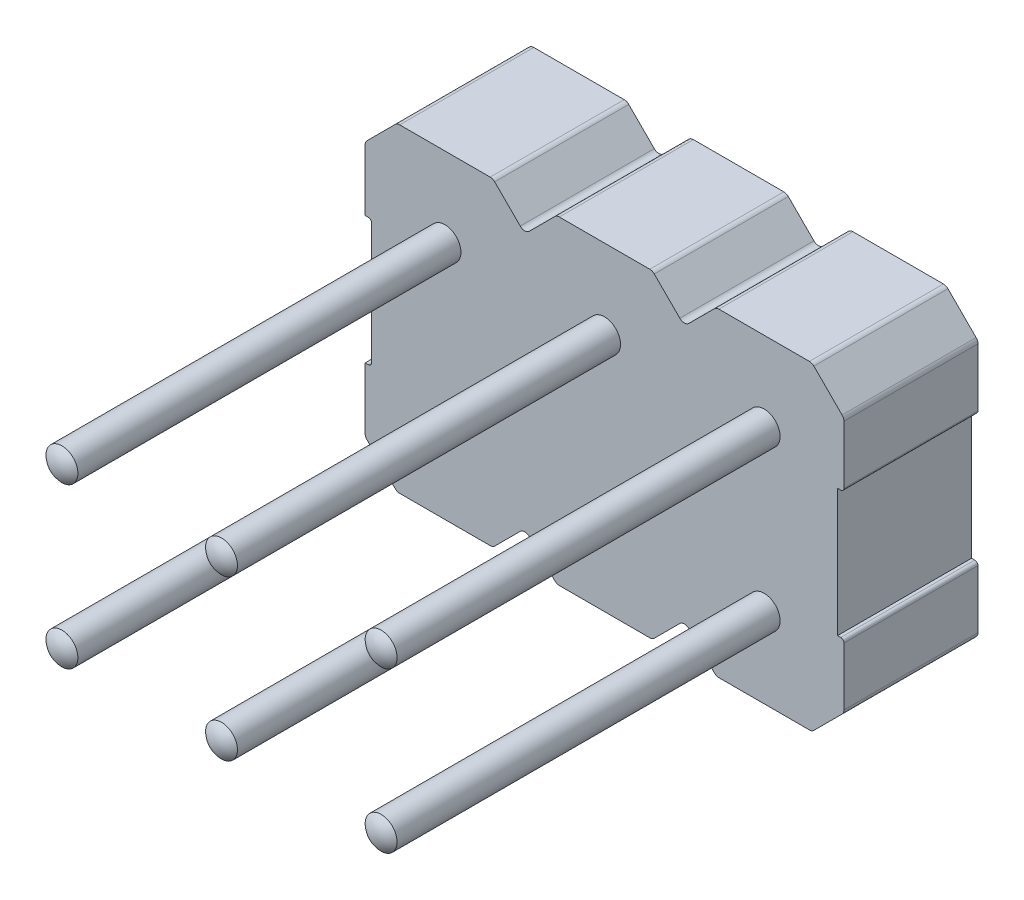
SolidWorks part; units mm, degrees
ref_plane "Plan de face" through (0, 0, 0) normal (0, 0, 1) x (1, 0, 0)
ref_plane "Plan de dessus" through (0, 0, 0) normal (0, 1, 0) x (1, 0, 0)
ref_plane "Plan de droite" through (0, 0, 0) normal (1, 0, 0) x (0, 0, -1)
sketch "Esquisse1" plane through (0, 0, 0) normal (0, 0, 1) x (1, 0, 0)
  line L0 (-1.25, 2) -> (-1.25, -2.5) construction
  line L1 (-3.2086, -2.5) -> (-1.7914, -2.5)
  line L2 (-3.75, -1.9586) -> (-3.75, -1)
  line L3 (-3.2086, 2.5) -> (-1.7914, 2.5)
  line L4 (3.75, -1.9586) -> (3.75, -1.05)
  line L5 (-3.75, -2.5) -> (3.75, 2.5) construction
  line L6 (-3.75, 2.5) -> (3.75, -2.5) construction
  line L7 (1.1793, 2.0707) -> (0.7793, 2.4707)
  line L8 (-1.7207, 2.4707) -> (-1.3207, 2.0707)
  line L9 (-1.1793, 2.0707) -> (-0.7793, 2.4707)
  line L10 (0, 0) -> (0, 1.0178) construction
  line L11 (-1.5641, 0) -> (0, 0) construction
  line L12 (1.7207, 2.4707) -> (1.3207, 2.0707)
  line L13 (1.7207, -2.4707) -> (1.3207, -2.0707)
  line L14 (1.1793, -2.0707) -> (0.7793, -2.4707)
  line L15 (-1.1793, -2.0707) -> (-0.7793, -2.4707)
  line L16 (-1.7207, -2.4707) -> (-1.3207, -2.0707)
  line L17 (-0.7086, 2.5) -> (0.7086, 2.5)
  line L18 (1.7914, 2.5) -> (3.2086, 2.5)
  line L19 (1.7914, -2.5) -> (3.2086, -2.5)
  line L20 (-0.7086, -2.5) -> (0.7086, -2.5)
  line L21 (3.7207, -2.0293) -> (3.2793, -2.4707)
  line L22 (3.7207, 2.0293) -> (3.2793, 2.4707)
  line L23 (-3.7207, -2.0293) -> (-3.2793, -2.4707)
  line L24 (-3.7207, 2.0293) -> (-3.2793, 2.4707)
  line L25 (-3.75, 1) -> (-3.75, 1.9586)
  line L26 (-3.75, -1) -> (-3.7, -1)
  line L27 (3.7, -1) -> (3.65, -1)
  line L28 (-3.75, 1) -> (-3.7, 1)
  line L29 (-3.65, -0.95) -> (-3.65, 0.95)
  line L30 (-3.75, 0) -> (-3.65, 1) construction
  line L31 (-3.75, 0) -> (-3.65, -1) construction
  line L32 (3.7, 1) -> (3.65, 1)
  line L33 (3.65, -1) -> (3.65, 1)
  line L34 (3.75, 1.05) -> (3.75, 1.9586)
  circle A0 centre (-2.5, 1.25) radius 0.25
  circle A1 centre (0, 1.25) radius 0.25
  circle A2 centre (2.5, 1.25) radius 0.25
  circle A3 centre (0, -1.25) radius 0.25
  circle A4 centre (2.5, -1.25) radius 0.25
  circle A5 centre (-2.5, -1.25) radius 0.25
  arc A6 (-3.2793, 2.4707) -> (-3.2086, 2.5) centre (-3.2086, 2.4) cw
  arc A7 (-3.7207, 2.0293) -> (-3.75, 1.9586) centre (-3.65, 1.9586) ccw
  arc A8 (-3.7207, -2.0293) -> (-3.75, -1.9586) centre (-3.65, -1.9586) cw
  arc A9 (-3.2793, -2.4707) -> (-3.2086, -2.5) centre (-3.2086, -2.4) ccw
  arc A10 (-1.7207, -2.4707) -> (-1.7914, -2.5) centre (-1.7914, -2.4) cw
  arc A11 (-1.1793, -2.0707) -> (-1.3207, -2.0707) centre (-1.25, -2.1414) ccw
  arc A12 (-0.7793, -2.4707) -> (-0.7086, -2.5) centre (-0.7086, -2.4) ccw
  arc A13 (0.7793, -2.4707) -> (0.7086, -2.5) centre (0.7086, -2.4) cw
  arc A14 (1.3207, -2.0707) -> (1.1793, -2.0707) centre (1.25, -2.1414) ccw
  arc A15 (1.7207, -2.4707) -> (1.7914, -2.5) centre (1.7914, -2.4) ccw
  arc A16 (3.2793, -2.4707) -> (3.2086, -2.5) centre (3.2086, -2.4) cw
  arc A17 (3.7207, -2.0293) -> (3.75, -1.9586) centre (3.65, -1.9586) ccw
  arc A18 (3.7207, 2.0293) -> (3.75, 1.9586) centre (3.65, 1.9586) cw
  arc A19 (3.2793, 2.4707) -> (3.2086, 2.5) centre (3.2086, 2.4) ccw
  arc A20 (1.7207, 2.4707) -> (1.7914, 2.5) centre (1.7914, 2.4) cw
  arc A21 (0.7793, 2.4707) -> (0.7086, 2.5) centre (0.7086, 2.4) ccw
  arc A22 (1.1793, 2.0707) -> (1.3207, 2.0707) centre (1.25, 2.1414) ccw
  arc A23 (-1.7207, 2.4707) -> (-1.7914, 2.5) centre (-1.7914, 2.4) ccw
  arc A24 (-0.7793, 2.4707) -> (-0.7086, 2.5) centre (-0.7086, 2.4) cw
  arc A25 (-1.3207, 2.0707) -> (-1.1793, 2.0707) centre (-1.25, 2.1414) ccw
  arc A26 (-3.7, -1) -> (-3.65, -0.95) centre (-3.7, -0.95) ccw
  arc A27 (-3.7, 1) -> (-3.65, 0.95) centre (-3.7, 0.95) cw
  arc A28 (3.7, -1) -> (3.75, -1.05) centre (3.7, -1.05) cw
  arc A29 (3.7, 1) -> (3.75, 1.05) centre (3.7, 1.05) ccw
  point P0 (0, 0)
  point P34 (-3.25, 2.5)
  point P47 (-3.75, 2)
  point P50 (-3.75, -2)
  point P53 (-3.25, -2.5)
  point P56 (-1.75, -2.5)
  point P59 (-1.25, -2)
  point P62 (-0.75, -2.5)
  point P65 (0.75, -2.5)
  point P68 (1.25, -2)
  point P71 (1.75, -2.5)
  point P74 (3.25, -2.5)
  point P77 (3.75, -2)
  point P80 (3.75, 2)
  point P83 (3.25, 2.5)
  point P86 (1.75, 2.5)
  point P89 (0.75, 2.5)
  point P92 (1.25, 2)
  point P95 (-1.75, 2.5)
  point P98 (-0.75, 2.5)
  point P102 (-3.75, 0)
  point P121 (3.75, -1)
  point P124 (3.75, 1)
  dimension "D9" = 0.5
  dimension "D12" = 0.1
  dimension "D13" = 0.05
  dimension "D1" = 7.5
  dimension "D2" = 5
  dimension "D3" = 2.5
  dimension "D4" = 0.5
  dimension "D5" = 0.5
  dimension "D6" = 45
  dimension "D7" = 1.25
  dimension "D8" = 1.25
  dimension "D10" = 3
  dimension "D11" = 2
extrude "Boss.-Extru.1" add sketch "Esquisse1" along normal blind 2.1
sketch "Esquisse2" plane through (0, 0, 2.1) normal (0, 0, 1) x (1, 0, 0)
  circle A0 centre (-2.5, 1.25) radius 0.25 construction
  circle A1 centre (-2.5, 1.25) radius 0.25
extrude "Boss.-Extru.2" add sketch "Esquisse2" along normal blind 6 separate body
dome "Dôme1" faces to dome 1 distance 0.1 reverse direction no elliptical dome no face at (-2.25, 1.25, 8.1) parameters "D1"=0.1
pattern_linear "Répétition linéaire2" count 3 spacing 2.5 along (1, 0, 0) count 2 spacing 2.5 along (0, -1, 0) of bodies 102
